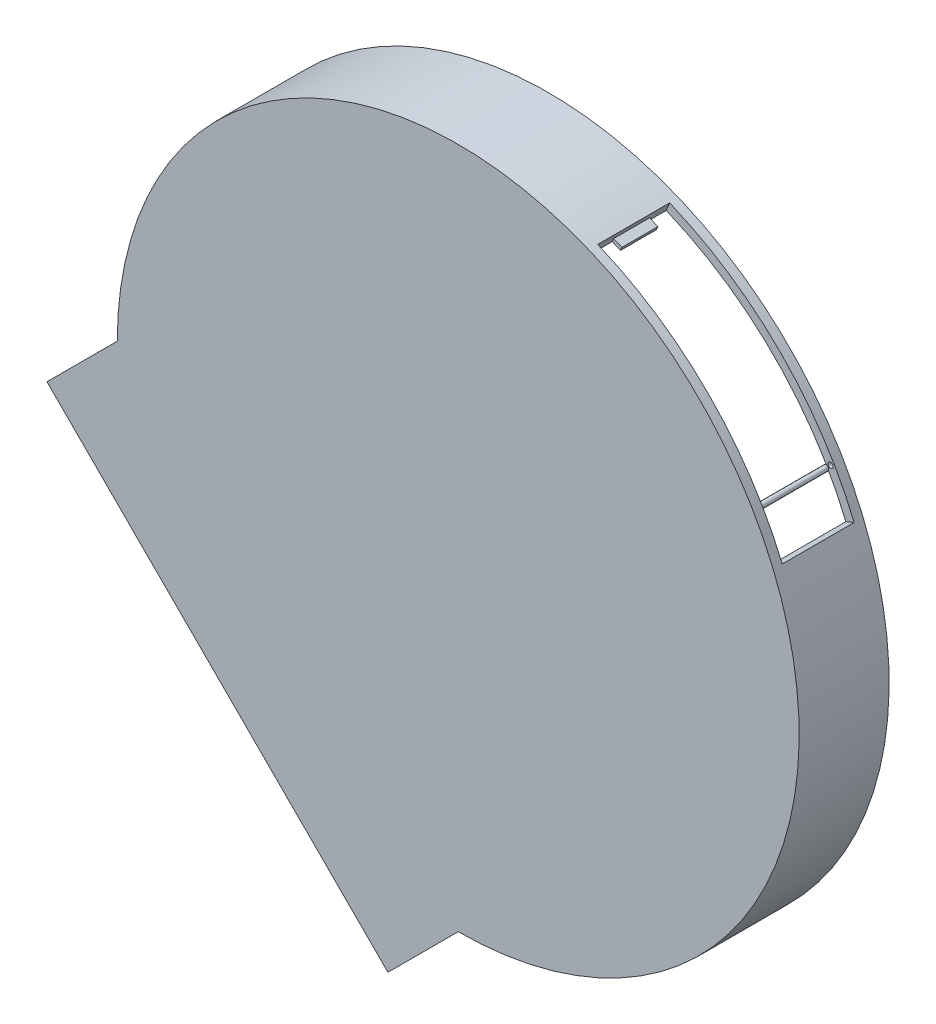
SolidWorks part; units mm, degrees
material "Plastique personnalisé"
ref_plane "Plan de face" through (0, 0, 0) normal (0, 0, 1) x (1, 0, 0)
ref_plane "Plan de dessus" through (0, 0, 0) normal (0, 1, 0) x (1, 0, 0)
ref_plane "Plan de droite" through (0, 0, 0) normal (1, 0, 0) x (0, 0, -1)
sketch "Esquisse1" plane through (0, 0, 0) normal (0, 0, 1) x (1, 0, 0)
  line L2 (0, -379) -> (-379, 0)
  line L3 (0, -379) -> (-78.1379, -457.1379)
  line L4 (-379, 0) -> (-457.1379, -78.1379)
  line L5 (-78.1379, -457.1379) -> (-457.1379, -78.1379)
  circle A0 centre (0, 0) radius 379
  dimension "D1" = 758
extrude "Boss.-Extru.1" add sketch "Esquisse1" along normal blind 100 contours L2 A0 | L2 A0 L5 | A0 L4 L5 | A0 L5 L3 region at (-221.3134, -221.3134, 0) region at (22.1157, 22.1157, 0) region at (-100.6174, -389.1122, 0) region at (-389.1122, -100.6174, 0)
sketch "Esquisse2" plane through (189.5, -189.5, 0) normal (0.7071, -0.7071, 0) x (0, 0, -1)
  line L1 (0, -267.9935) -> (-100, -378.4972)
  line L3 (0, -267.9935) -> (0, -378.4972)
  line L4 (-100, -378.4972) -> (0, -378.4972) construction
  line L5 (0, -267.9935) -> (0, -378.4972) construction
  line L6 (0, -378.4972) -> (-100, -378.4972)
extrude "Enlèv. mat.-Extru.2" cut sketch "Esquisse2" against normal blind 570
shell "Coque3" thickness 10 removed face at (39.2467, 39.2467, 0)
sketch "Esquisse3" plane through (0, 0, 90) normal (0, 0, -1) x (-1, 0, 0)
  line L1 (-350.1503, 145.037) -> (0, 0)
  line L2 (0, 0) -> (-145.037, 350.1503)
  arc A0 (379, 0) -> (0, -379) centre (0, 0) ccw construction
  arc A1 (-267.9935, 267.9935) -> (-145.037, 350.1503) centre (0, 0) cw
  arc A2 (-267.9935, 267.9935) -> (-350.1503, 145.037) centre (0, 0) ccw
  dimension "D1" = 22.5
  dimension "D2" = 22.5
extrude "Enlèv. mat.-Extru.4" cut sketch "Esquisse3" along normal blind 80
sketch "Esquisse5" plane through (0, 0, 90) normal (0, 0, -1) x (-1, 0, 0)
  line L0 (0, 0) -> (-267.9935, 267.9935)
  arc A0 (-145.037, 350.1503) -> (-350.1503, 145.037) centre (0, 0) ccw construction
  circle A1 centre (-323.8935, 187) radius 3
  arc A2 (-323.8935, 187) -> (-264.4579, 264.4579) centre (0, 0) cw
  dimension "D2" = 6
extrude "Boss.-Extru.3" add sketch "Esquisse5" along normal blind 85 and the other way blind 5 contours A1 region at (326.421, 185.5475, 90)
sketch "Esquisse7" plane through (0, 0, 0) normal (0, 0, -1) x (-1, 0, 0)
  arc A0 (-267.9935, 267.9935) -> (-328.2236, 189.5) centre (0, 0) ccw
  arc A1 (379, 0) -> (0, -379) centre (0, 0) ccw construction
  circle A3 centre (-323.8935, 187) radius 3
  dimension "D1" = 6
  dimension "D2" = 15
extrude "Enlèv. mat.-Extru.12" cut sketch "Esquisse7" against normal blind 15 contours A3 region at (323.8935, 187, 0)
sketch "Esquisse10" plane through (-85.3178, -85.3178, -133.3311) normal (-0.4745, -0.4745, -0.7415) x (-0.8803, 0.2557, 0.3996)
  line L0 (333.6248, 0) -> (-96.9216, -319.2362)
  line L1 (118.3516, -159.6181) -> (207.1168, -279.3336)
  line L2 (-8.1564, -438.9517) -> (422.39, -119.7155) construction
  line L3 (145.4416, -288.9197) -> (234.2067, -223.1032)
  line L4 (145.4416, -288.9197) -> (109.7053, -240.723)
  line L5 (234.2067, -223.1032) -> (198.4705, -174.9065)
  line L6 (109.7053, -240.723) -> (198.4705, -174.9065)
  line L7 (145.4416, -288.9197) -> (198.4705, -174.9065) construction
  line L8 (234.2067, -223.1032) -> (109.7053, -240.723) construction
  point P9 (171.956, -231.9131)
  dimension "D1" = 60
  dimension "D2" = 110.5037
  dimension "D3" = 90
extrude "Enlèv. mat.-Extru.13" cut sketch "Esquisse10" against normal blind 10 contours L6 L4 L3 L1 | L6 L1 L3 L5 region at (-256.2212, -217.1522, 60.389) region at (-217.1522, -256.2212, 60.389)
sketch "Esquisse12" plane through (0, 0, 0) normal (0.9239, -0.3827, 0) x (0, 0, -1)
  line L0 (-10, 369) -> (-90, 369) construction
  line L1 (-70, 369) -> (-30, 369)
  line L2 (-70, 369) -> (-70, 373)
  line L3 (-70, 373) -> (-30, 373)
  line L4 (-30, 369) -> (-30, 373)
  line L5 (-90, 369) -> (-50, 369)
  line M4 (-90, 369) -> (-10, 369)
  dimension "D1" = 40
  dimension "D2" = 40
  dimension "D4" = 4
extrude "Boss.-Extru.27" add sketch "Esquisse12" along normal blind 10 contours L1 L4 L3 L2 M4 region at (141.9756, 342.7593, 50)
